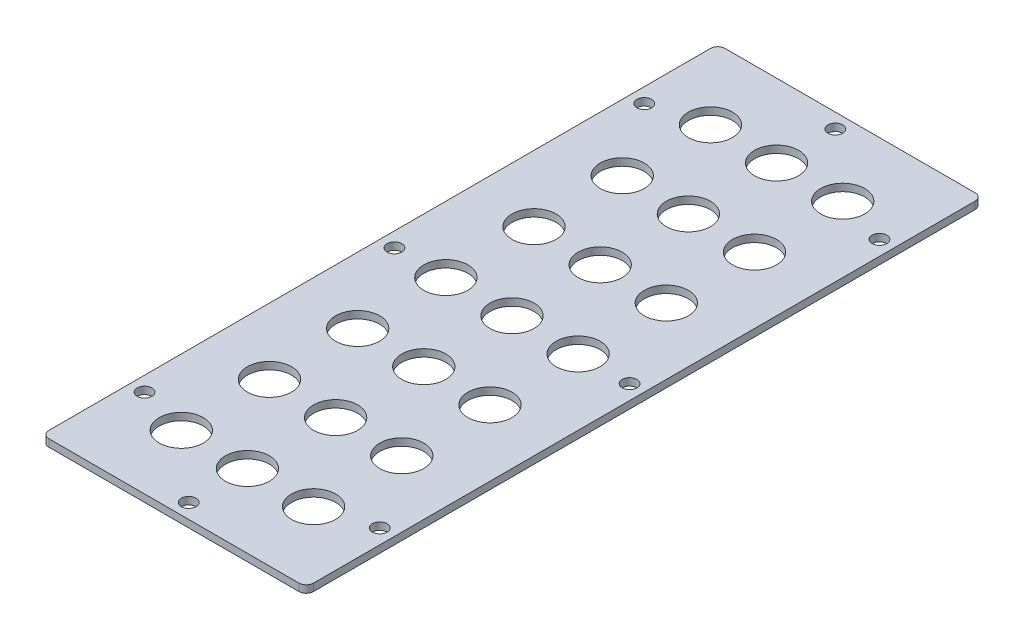
SolidWorks part; units mm, degrees
material "PC High Viscosity"
ref_plane "Front Plane" through (0, 0, 0) normal (0, 0, 1) x (1, 0, 0)
ref_plane "Top Plane" through (0, 0, 0) normal (0, 1, 0) x (1, 0, 0)
ref_plane "Right Plane" through (0, 0, 0) normal (1, 0, 0) x (0, 0, -1)
sketch "Sketch1" plane through (0, 0, 0) normal (0, 1, 0) x (1, 0, 0)
  line L1 (-57.15, -146.05) -> (57.15, -146.05)
  line L2 (-57.15, -146.05) -> (-57.15, 146.05)
  line L3 (-57.15, 146.05) -> (57.15, 146.05)
  line L4 (57.15, -146.05) -> (57.15, 146.05)
  line L5 (-57.15, -146.05) -> (57.15, 146.05) construction
  line L6 (-57.15, 146.05) -> (57.15, -146.05) construction
  point P0 (0, 0)
  dimension "D1" = 292.1
  dimension "D2" = 114.3
extrude "Boss-Extrude1" add sketch "Sketch1" along normal blind 3.175
sketch "Sketch2" plane through (0, 3.175, 0) normal (0, 1, 0) x (1, 0, 0)
  line L0 (-57.15, 114.3) -> (-28.575, 114.3) construction
  line L2 (-28.575, 114.3) -> (0, 114.3) construction
  line L3 (0, 114.3) -> (28.575, 114.3) construction
  line L4 (28.575, 114.3) -> (57.15, 114.3) construction
  circle A0 centre (-28.575, 114.3) radius 9.525
  circle A1 centre (0, 114.3) radius 9.525
  circle A2 centre (28.575, 114.3) radius 9.525
  dimension "D1" = 19.05
  dimension "D2" = 28.575
  dimension "D3" = 114.3
extrude "Cut-Extrude1" cut sketch "Sketch2" against normal through all
sketch "Sketch4" plane through (0, 3.175, 0) normal (0, 1, 0) x (1, 0, 0)
  line L0 (57.15, 146.05) -> (-57.15, 146.05) construction
  line L1 (57.15, -146.05) -> (57.15, 146.05) construction
  line L2 (-57.15, 146.05) -> (-57.15, -146.05) construction
  line L3 (-57.15, -146.05) -> (57.15, -146.05) construction
  circle A0 centre (-50.8, 0) radius 3.175
  circle A1 centre (50.8, 0) radius 3.175
  circle A2 centre (0, 139.7) radius 3.175
  circle A3 centre (0, -139.7) radius 3.175
  dimension "D5" = 6.35
  dimension "D1" = 6.35
  dimension "D2" = 6.35
  dimension "D3" = 6.35
  dimension "D4" = 6.35
extrude "Cut-Extrude2" cut sketch "Sketch4" against normal through all
pattern_linear "LPattern2" count 2 spacing 107.95 along (0, 0, -1) count 2 spacing 107.95 along (0, 0, 1) of face at (-50.8, 0, 3.175) of face at (50.8, 0, 3.175)
fillet "Fillet1" radius 3.175 4 edges at (-57.15, 1.5875, -146.05) (57.15, 1.5875, -146.05) (-57.15, 1.5875, 146.05) (57.15, 1.5875, 146.05)
pattern_linear "LPattern3" count 7 spacing 38.1 along (0, 0, 1) of "Cut-Extrude1"
equation "\"D2@Sketch4\"=\"D1@Sketch4\""
equation "\"D3@Sketch4\"=\"D1@Sketch4\""
equation "\"D4@Sketch4\"=\"D1@Sketch4\""
